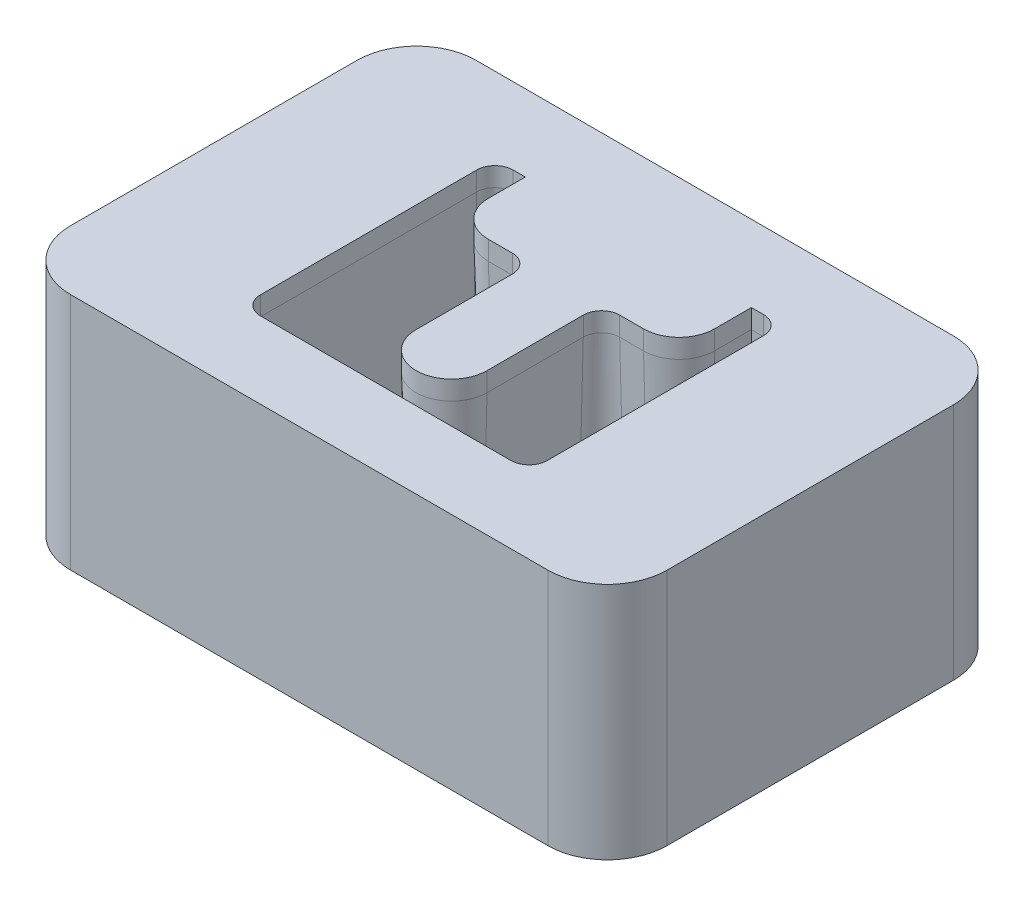
SolidWorks part; units mm, degrees
material "K110"
ref_plane "Front Plane" through (0, 0, 0) normal (0, 0, 1) x (1, 0, 0)
ref_plane "Top Plane" through (0, 0, 0) normal (0, 1, 0) x (1, 0, 0)
ref_plane "Right Plane" through (0, 0, 0) normal (1, 0, 0) x (0, 0, -1)
sketch "Sketch1" plane through (0, 0, 0) normal (0, 1, 0) x (1, 0, 0)
  line L1 (-50, -34) -> (50, -34)
  line L2 (-50, -34) -> (-50, 34)
  line L3 (-50, 34) -> (50, 34)
  line L4 (50, -34) -> (50, 34)
  line L5 (-50, -34) -> (50, 34) construction
  line L6 (-50, 34) -> (50, -34) construction
  point P0 (0, 0)
  dimension "D1" = 68
  dimension "D2" = 100
extrude "Boss-Extrude1" add sketch "Sketch1" against normal blind 40
fillet "Fillet1" radius 10 4 edges at (-50, -20, -34) (50, -20, -34) (50, -20, 34) (-50, -20, 34)
sketch "Sketch2" plane through (0, 0, 0) normal (0, 1, 0) x (1, 0, 0)
  line L22 (-21, -21.18) -> (21, -21.18)
  line L23 (-24.05, 18.13) -> (-24.05, -18.13)
  line L24 (-18.95, 21.18) -> (-21, 21.18)
  line L25 (-18.95, 15) -> (-18.95, 21.18)
  line L26 (-9, 9.05) -> (-13, 9.05)
  line L27 (-5.95, -10.13) -> (-5.95, 6)
  line L28 (5.95, 6) -> (5.95, -10.13)
  line L29 (13, 9.05) -> (9, 9.05)
  line L30 (18.95, 21.18) -> (18.95, 15)
  line L31 (21, 21.18) -> (18.95, 21.18)
  line L32 (24.05, -18.13) -> (24.05, 18.13)
  line L33 (-21, -21.18) -> (21, -21.18)
  line L34 (-24.05, 18.13) -> (-24.05, -18.13)
  line L35 (-18.95, 21.18) -> (-21, 21.18)
  line L36 (-18.95, 15) -> (-18.95, 21.18)
  line L37 (-9, 9.05) -> (-13, 9.05)
  line L38 (-5.95, -10.13) -> (-5.95, 6)
  line L39 (5.95, 6) -> (5.95, -10.13)
  line L40 (13, 9.05) -> (9, 9.05)
  line L41 (18.95, 21.18) -> (18.95, 15)
  line L42 (21, 21.18) -> (18.95, 21.18)
  line L43 (24.05, -18.13) -> (24.05, 18.13)
  arc A18 (21, -21.18) -> (24.05, -18.13) centre (21, -18.13) ccw
  arc A19 (-24.05, -18.13) -> (-21, -21.18) centre (-21, -18.13) ccw
  arc A20 (-21, 21.18) -> (-24.05, 18.13) centre (-21, 18.13) ccw
  arc A21 (-18.95, 15) -> (-13, 9.05) centre (-13, 15) ccw
  arc A22 (-5.95, 6) -> (-9, 9.05) centre (-9, 6) ccw
  arc A23 (-5.95, -10.13) -> (5.95, -10.13) centre (0, -10.13) ccw
  arc A24 (9, 9.05) -> (5.95, 6) centre (9, 6) ccw
  arc A25 (13, 9.05) -> (18.95, 15) centre (13, 15) ccw
  arc A26 (24.05, 18.13) -> (21, 21.18) centre (21, 18.13) ccw
  arc A27 (21, -21.18) -> (24.05, -18.13) centre (21, -18.13) ccw
  arc A28 (-24.05, -18.13) -> (-21, -21.18) centre (-21, -18.13) ccw
  arc A29 (-21, 21.18) -> (-24.05, 18.13) centre (-21, 18.13) ccw
  arc A30 (-18.95, 15) -> (-13, 9.05) centre (-13, 15) ccw
  arc A31 (-5.95, 6) -> (-9, 9.05) centre (-9, 6) ccw
  arc A32 (-5.95, -10.13) -> (5.95, -10.13) centre (0, -10.13) ccw
  arc A33 (9, 9.05) -> (5.95, 6) centre (9, 6) ccw
  arc A34 (13, 9.05) -> (18.95, 15) centre (13, 15) ccw
  arc A35 (24.05, 18.13) -> (21, 21.18) centre (21, 18.13) ccw
  dimension "D1" = 0.05
extrude "Cut-Extrude1" cut sketch "Sketch2" against normal up to next
sketch "Sketch3" plane through (0, 0, 0) normal (0, 0, 1) x (1, 0, 0)
  line L6 (24.05, -3.2) -> (25.0136, -40)
  line L7 (40, -40) -> (40, 0) construction
  line L8 (40, -40) -> (50, -40) construction
  line L11 (37.4, 0) -> (-37.4, 0) construction
  line L12 (25.0136, -40) -> (23.05, -40)
  line L13 (-40, -40) -> (40, -40) construction
  line L14 (23.05, -3.2) -> (24.05, -3.2)
  line L15 (23.05, -40) -> (23.05, -3.2)
  line L16 (24.05, -40) -> (24.05, 0) construction
  dimension "D1" = 3.2
  dimension "D2" = 1.5
  dimension "D3" = 1
sketch "Sketch5" plane through (0, 0, 0) normal (0, 1, 0) x (1, 0, 0)
  line L0 (21, 21.18) -> (18.95, 21.18) construction
  line L1 (24.05, -18.13) -> (24.05, 18.13) construction
  line L2 (18.95, 21.18) -> (18.95, 15) construction
  line L3 (13, 9.05) -> (9, 9.05) construction
  line L4 (5.95, 6) -> (5.95, -10.13) construction
  line L5 (-5.95, -10.13) -> (-5.95, 6) construction
  line L6 (-9, 9.05) -> (-13, 9.05) construction
  line L7 (-18.95, 15) -> (-18.95, 21.18) construction
  line L8 (-18.95, 21.18) -> (-21, 21.18) construction
  line L9 (-24.05, 18.13) -> (-24.05, -18.13) construction
  line L10 (-21, -21.18) -> (21, -21.18) construction
  line L11 (-21, -21.18) -> (21, -21.18)
  line L12 (-24.05, 18.13) -> (-24.05, -18.13)
  line L13 (-18.95, 21.18) -> (-21, 21.18)
  line L14 (-18.95, 15) -> (-18.95, 21.18)
  line L15 (-9, 9.05) -> (-13, 9.05)
  line L16 (-5.95, -10.13) -> (-5.95, 6)
  line L17 (5.95, 6) -> (5.95, -10.13)
  line L18 (13, 9.05) -> (9, 9.05)
  line L19 (18.95, 21.18) -> (18.95, 15)
  line L20 (24.05, -18.13) -> (24.05, 18.13)
  line L21 (21, 21.18) -> (18.95, 21.18)
  arc A0 (-5.95, 6) -> (-9, 9.05) centre (-9, 6) ccw construction
  arc A1 (24.05, 18.13) -> (21, 21.18) centre (21, 18.13) ccw construction
  arc A2 (13, 9.05) -> (18.95, 15) centre (13, 15) ccw construction
  arc A3 (9, 9.05) -> (5.95, 6) centre (9, 6) ccw construction
  arc A4 (-5.95, -10.13) -> (5.95, -10.13) centre (0, -10.13) ccw construction
  arc A5 (-18.95, 15) -> (-13, 9.05) centre (-13, 15) ccw construction
  arc A6 (-21, 21.18) -> (-24.05, 18.13) centre (-21, 18.13) ccw construction
  arc A7 (-24.05, -18.13) -> (-21, -21.18) centre (-21, -18.13) ccw construction
  arc A8 (21, -21.18) -> (24.05, -18.13) centre (21, -18.13) ccw construction
  arc A9 (21, -21.18) -> (24.05, -18.13) centre (21, -18.13) ccw
  arc A10 (-24.05, -18.13) -> (-21, -21.18) centre (-21, -18.13) ccw
  arc A11 (-21, 21.18) -> (-24.05, 18.13) centre (-21, 18.13) ccw
  arc A12 (-18.95, 15) -> (-13, 9.05) centre (-13, 15) ccw
  arc A13 (-5.95, 6) -> (-9, 9.05) centre (-9, 6) ccw
  arc A14 (-5.95, -10.13) -> (5.95, -10.13) centre (0, -10.13) ccw
  arc A15 (9, 9.05) -> (5.95, 6) centre (9, 6) ccw
  arc A16 (13, 9.05) -> (18.95, 15) centre (13, 15) ccw
  arc A17 (24.05, 18.13) -> (21, 21.18) centre (21, 18.13) ccw
sweep "Cut-Sweep1" cut profiles "Sketch3" path "Sketch5"
hole_wizard "M6 Tapped Hole1" positions "Sketch11" profile "Sketch9" tap size "M6" standard "ISO"
sketch "Sketch11" plane through (0, -40, 0) normal (0, -1, 0) x (-1, 0, 0)
  line L0 (-40, 34) -> (40, 34) construction
  line L1 (-50, -24) -> (-50, 24) construction
  line L2 (50, 24) -> (50, -24) construction
  line L3 (40, -34) -> (-40, -34) construction
  point P0 (-43, 27)
  point P2 (43, 27)
  point P4 (43, -27)
  point P6 (-43, -27)
  dimension "D1" = 7
  dimension "D2" = 7
  dimension "D3" = 7
  dimension "D4" = 7
sketch "Sketch9" plane through (43, -40, -27) normal (1, 0, 0) x (0, 0, -1)
  line L0 (0, 0) -> (0, 18.5022)
  line L1 (0, 18.5022) -> (2.5, 17)
  line L2 (2.5, 17) -> (2.5, 0.525)
  line L3 (2.5, 0.525) -> (3.025, 0)
  line L5 (3.025, 0) -> (0, 0)
  line L6 (-2.5, 0.525) -> (-3.025, 0) construction
  line L10 (0, 18.5022) -> (-2.5, 17) construction
  line L11 (0, -6.35) -> (0, 107.95) construction
  dimension "Tap Drill Dia." = 5
  dimension "Tap Drill Depth" = 17
  dimension "Near C'Sink Dia." = 6.05
  dimension "Near C'Sink Angle" = 90
  dimension "Drill Angle" = 118
cosmetic thread "Hole Thread1"
cosmetic thread "Hole Thread2"
cosmetic thread "Hole Thread3"
cosmetic thread "Hole Thread4"
